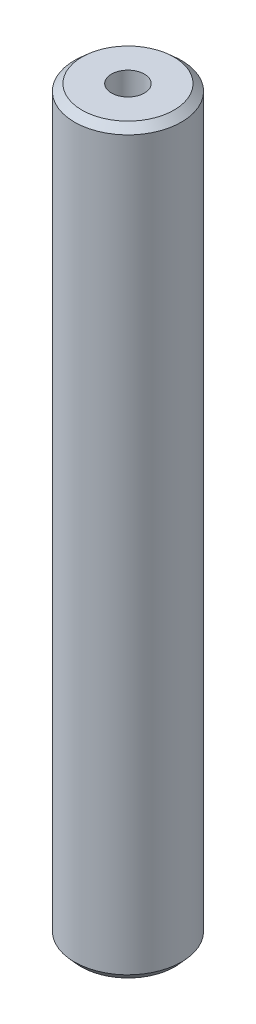
SolidWorks part; units mm, degrees
ref_plane "Front Plane" through (0, 0, 0) normal (0, 0, 1) x (1, 0, 0)
ref_plane "Top Plane" through (0, 0, 0) normal (0, 1, 0) x (1, 0, 0)
ref_plane "Right Plane" through (0, 0, 0) normal (1, 0, 0) x (0, 0, -1)
sketch "Sketch1" plane through (0, 0, 0) normal (0, 1, 0) x (1, 0, 0)
  circle A0 centre (0, 0) radius 10
  dimension "SHAFT_OD" = 20
extrude "Boss-Extrude1" add sketch "Sketch1" along normal blind 138.6382
sketch "Sketch2" plane through (0, 0, 0) normal (0, 1, 0) x (1, 0, 0)
  circle A0 centre (0, 0) radius 3.0784
  dimension "BORE_D" = 6.1568
extrude "Cut-Extrude1" cut sketch "Sketch2" along normal through all
chamfer "Chamfer1" distance 1.2417 angle 48.332 2 edges at (0, 138.6382, 10) (0, 0, 10) first distance on face at (0, 138.6382, 10) first distance on face at (0, 0, 3.0784)
